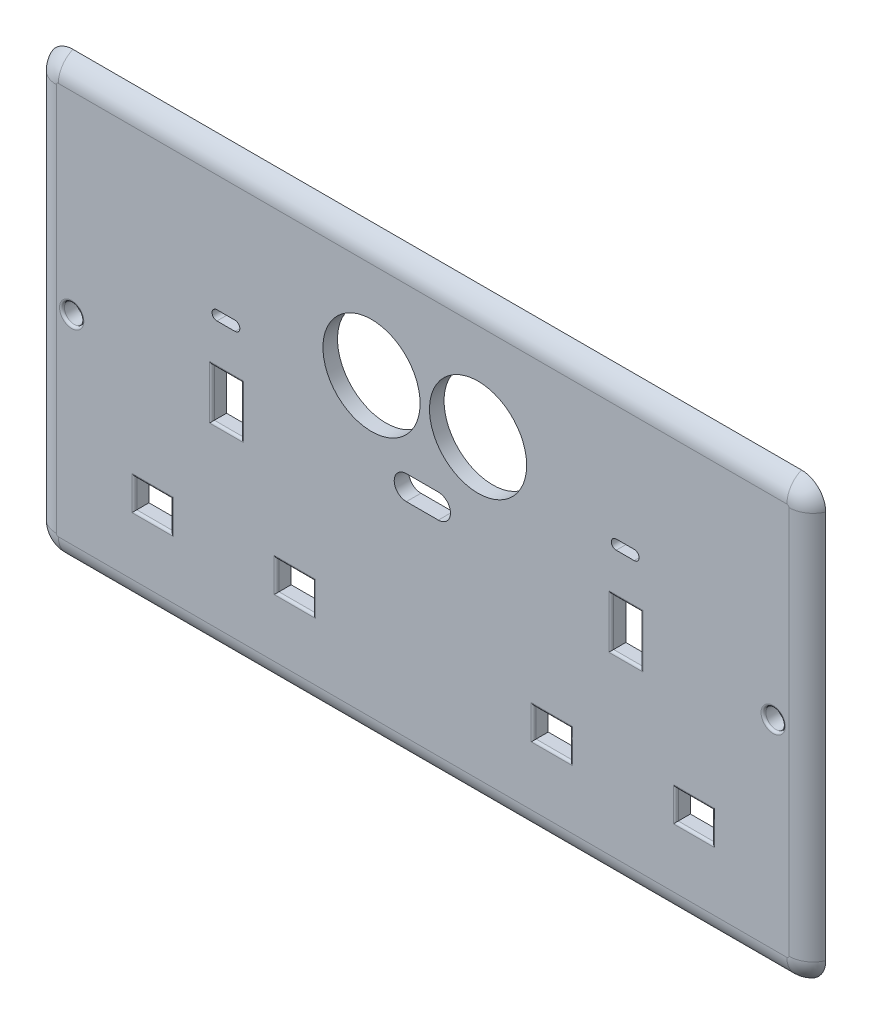
SolidWorks part; units mm, degrees
ref_plane "Front Plane" through (0, 0, 0) normal (0, 0, 1) x (1, 0, 0)
ref_plane "Top Plane" through (0, 0, 0) normal (0, 1, 0) x (1, 0, 0)
ref_plane "Right Plane" through (0, 0, 0) normal (1, 0, 0) x (0, 0, -1)
sketch "Sketch1" plane through (0, 0, 0) normal (0, 0, 1) x (1, 0, 0)
  line L1 (-111.6279, -20.9302) -> (48.3721, -20.9302)
  line L2 (-111.6279, -20.9302) -> (-111.6279, -110.9302)
  line L3 (-111.6279, -110.9302) -> (48.3721, -110.9302)
  line L4 (48.3721, -20.9302) -> (48.3721, -110.9302)
  dimension "D1" = 160
  dimension "D2" = 90
extrude "Boss-Extrude8" add sketch "Sketch1" along normal blind 3 contours L1 L4 L3 L2
fillet "Fillet15" radius 5 4 edges at (-111.6279, -20.9302, 1.5) (-111.6279, -110.9302, 1.5) (48.3721, -20.9302, 1.5) (48.3721, -110.9302, 1.5)
fillet "Fillet16" radius 5 8 edges at (-110.1634, -22.3947, 3) (-31.6279, -20.9302, 3) (46.9076, -22.3947, 3) (48.3721, -65.9302, 3) (46.9076, -109.4658, 3) (-31.6279, -110.9302, 3) (-110.1634, -109.4658, 3) (-111.6279, -65.9302, 3)
sketch "Sketch14" plane through (0, 0, 3) normal (0, 0, 1) x (1, 0, 0)
  line L0 (-61.6933, -87.9391) -> (-54.1933, -87.9391)
  line L1 (-74.995, -60.0022) -> (-68.995, -60.0022)
  line L2 (-74.995, -60.0022) -> (-74.995, -70.0022)
  line L3 (-74.995, -70.0022) -> (-68.995, -70.0022)
  line L4 (-68.995, -60.0022) -> (-68.995, -70.0022)
  line L5 (-90.9675, -87.9609) -> (-83.4675, -87.9609)
  line L6 (-90.9675, -87.9609) -> (-90.9675, -93.9609)
  line L7 (-90.9675, -93.9609) -> (-83.4675, -93.9609)
  line L8 (-83.4675, -87.9609) -> (-83.4675, -93.9609)
  line L9 (-61.6933, -87.9391) -> (-61.6933, -93.9391)
  line L10 (-61.6933, -93.9391) -> (-54.1933, -93.9391)
  line L11 (-54.1933, -87.9391) -> (-54.1933, -93.9391)
  line L12 (-73.9755, -50.54) -> (-70.2594, -50.54) construction
  line L13 (-73.9755, -49.54) -> (-70.2594, -49.54)
  line L14 (-73.9755, -51.54) -> (-70.2594, -51.54)
  line L15 (20.5112, -87.7116) -> (28.0112, -87.7116)
  line L16 (7.2095, -59.7748) -> (13.2095, -59.7748)
  line L17 (7.2095, -59.7748) -> (7.2095, -69.7748)
  line L18 (7.2095, -69.7748) -> (13.2095, -69.7748)
  line L19 (13.2095, -59.7748) -> (13.2095, -69.7748)
  line L20 (-8.763, -87.7335) -> (-1.263, -87.7335)
  line L21 (-8.763, -87.7335) -> (-8.763, -93.7335)
  line L22 (-8.763, -93.7335) -> (-1.263, -93.7335)
  line L23 (-1.263, -87.7335) -> (-1.263, -93.7335)
  line L24 (20.5112, -87.7116) -> (20.5112, -93.7116)
  line L25 (20.5112, -93.7116) -> (28.0112, -93.7116)
  line L26 (28.0112, -87.7116) -> (28.0112, -93.7116)
  line L27 (8.2289, -50.3125) -> (11.9451, -50.3125) construction
  line L28 (8.2289, -49.3125) -> (11.9451, -49.3125)
  line L29 (8.2289, -51.3125) -> (11.9451, -51.3125)
  line L30 (-34.9761, -61.7555) -> (-28.3892, -61.7555) construction
  line L33 (-34.9761, -59.2555) -> (-28.3892, -59.2555)
  line L34 (-34.9761, -64.2555) -> (-28.3892, -64.2555)
  arc A0 (-73.9755, -49.54) -> (-73.9755, -51.54) centre (-73.9755, -50.54) ccw
  arc A1 (-70.2594, -51.54) -> (-70.2594, -49.54) centre (-70.2594, -50.54) ccw
  arc A2 (8.2289, -49.3125) -> (8.2289, -51.3125) centre (8.2289, -50.3125) ccw
  arc A3 (11.9451, -51.3125) -> (11.9451, -49.3125) centre (11.9451, -50.3125) ccw
  circle A4 centre (-42.1468, -45.3411) radius 10
  circle A9 centre (-103.8786, -65.3411) radius 2
  circle A10 centre (40.5525, -65.3411) radius 2
  arc A11 (-34.9761, -59.2555) -> (-34.9761, -64.2555) centre (-34.9761, -61.7555) ccw
  arc A12 (-28.3892, -64.2555) -> (-28.3892, -59.2555) centre (-28.3892, -61.7555) ccw
  circle A13 centre (-20.2112, -45.3874) radius 10
  point P14 (-72.1175, -50.54)
  point P33 (10.087, -50.3125)
  point P44 (-31.6826, -61.7555)
extrude "Cut-Extrude1" cut sketch "Sketch14" against normal blind 3
fillet "Fillet17" radius 0.5 26 edges at (42.5525, -65.3411, 3) (-101.8786, -65.3411, 3) (13.2095, -64.7748, 3) (10.2095, -69.7748, 3) (7.2095, -64.7748, 3) (10.2095, -59.7748, 3) (-1.263, -90.7335, 3) (-5.013, -93.7335, 3) (-8.763, -90.7335, 3) (-5.013, -87.7335, 3) (20.5112, -90.7116, 3) (24.2612, -93.7116, 3) (28.0112, -90.7116, 3) (24.2612, -87.7116, 3) (-54.1933, -90.9391, 3) (-61.6933, -90.9391, 3) (-57.9433, -87.9391, 3) (-57.9433, -93.9391, 3) (-83.4675, -90.9609, 3) (-87.2175, -93.9609, 3) (-90.9675, -90.9609, 3) (-87.2175, -87.9609, 3) (-71.995, -70.0022, 3) (-68.995, -65.0022, 3) (-74.995, -65.0022, 3) (-71.995, -60.0022, 3)
